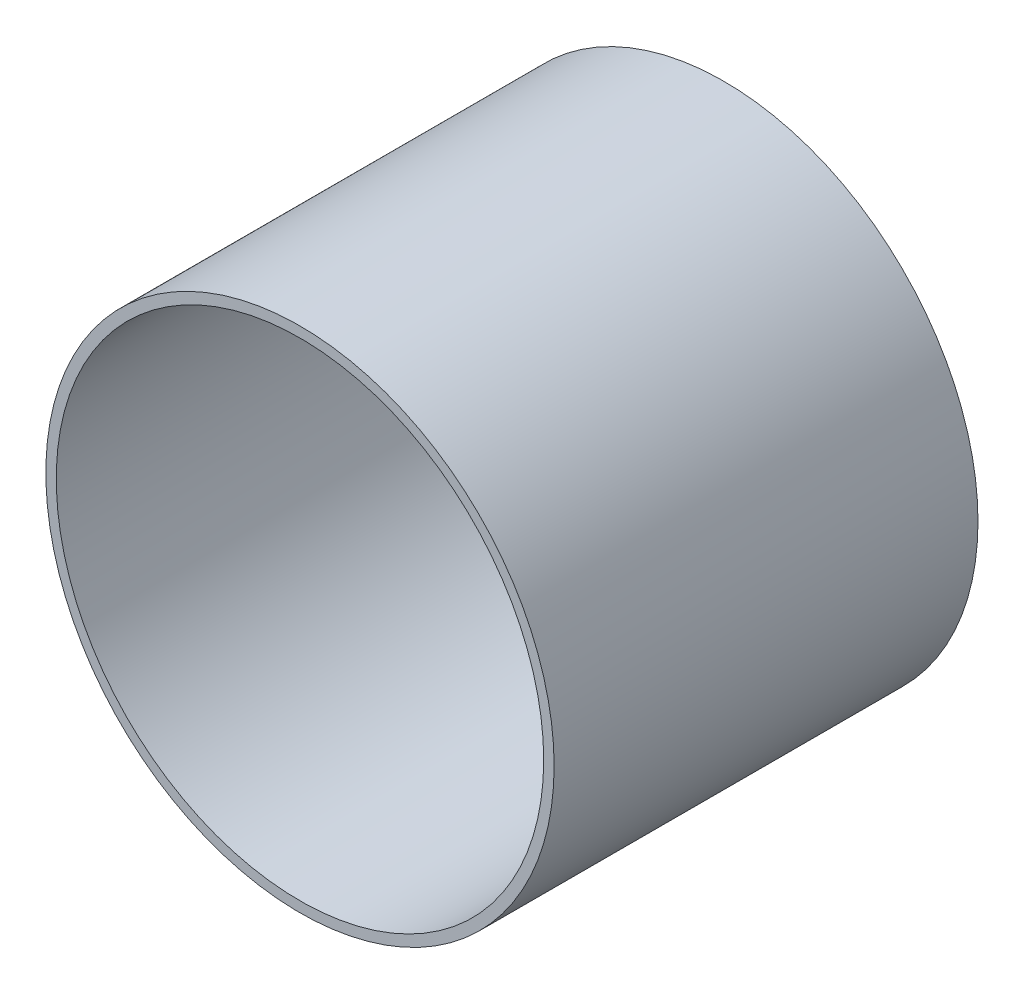
SolidWorks part; units mm, degrees
ref_plane "Front Plane" through (0, 0, 0) normal (0, 0, 1) x (1, 0, 0)
ref_plane "Top Plane" through (0, 0, 0) normal (0, 1, 0) x (1, 0, 0)
ref_plane "Right Plane" through (0, 0, 0) normal (1, 0, 0) x (0, 0, -1)
sketch "Sketch1" plane through (0, 0, 0) normal (0, 0, 1) x (1, 0, 0)
  circle A0 centre (0, 0) radius 38.0746
  circle A1 centre (0, 0) radius 36.5125
  dimension "D1" = 73.025
  dimension "D2" = 76.1492
extrude "Boss-Extrude1" add sketch "Sketch1" along normal mid plane 63.5
equation "\"AIRFRAME_OD\"= 3.142in"
equation "\"AIRFRAME_ID\"= 3.00in"
equation "\"FLAT_T\"= 0.125in"
equation "\"NOSE_EXP_L\"= 3.5in"
equation "\"NOSE_SHOULDER_L\"= 1.5in"
equation "\"MAIN_L\"= 30in"
equation "\"RECO_COUP_L\"= 6in"
equation "\"RECO_SWITCH_L\"= 1.5in"
equation "\"DROGUE_L\"= 14in"
equation "\"ATS_FORE_COUP_L\"= 4in"
equation "\"ATS_AFT_COUP_L\"= 2.5in"
equation "\"LOWER_L\"= 16in"
equation "\"FIN_N\"= 4"
equation "\"CR_AFT_X\"= 0.5in"
equation "\"CR_FORE_X\"= 6in"
equation "\"D1@Sketch1\"=\"COUPLER_ID\""
equation "\"D2@Sketch1\"=\"COUPLER_OD\""
equation "\"D1@Boss-Extrude1\"=\"ATS_AFT_COUP_L\""
equation "\"FIN_ROOT\"= 5in"
equation "\"FIN_X\"= 0.75in"
equation "\"MOTOR_OD\"= 2.25in"
equation "\"MOTOR_ID\"= 2.126in"
equation "\"COUPLER_OD\"= 2.998in"
equation "\"COUPLER_ID\"= 2.875in"
equation "\"RECO_ROD_X\"= 1.5in"
equation "\"ATS_ROD_X\"= 2in"
equation "\"MOTOR_L\"= 8in"
equation "\"MOTOR_LOWER_X\"= 0.5in"
